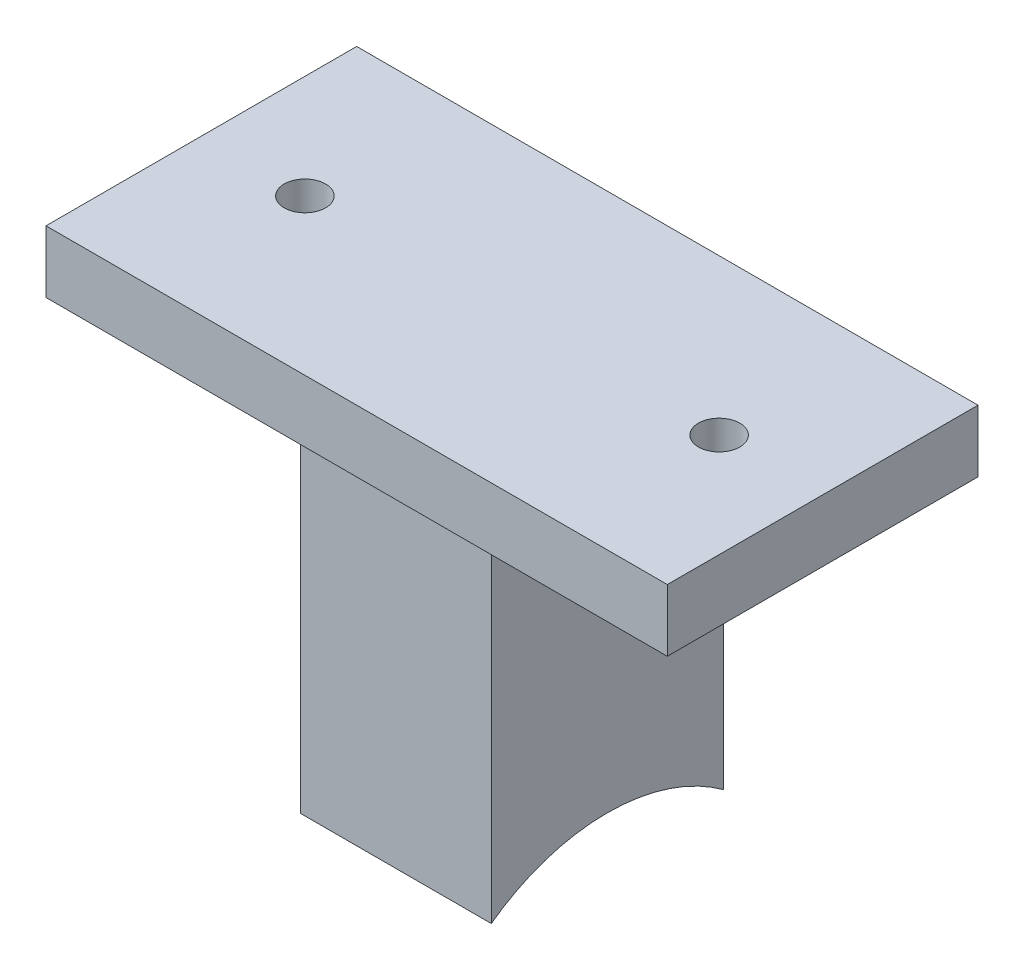
SolidWorks part; units mm, degrees
ref_plane "前视基准面" through (0, 0, 0) normal (0, 0, 1) x (1, 0, 0)
ref_plane "上视基准面" through (0, 0, 0) normal (0, 1, 0) x (1, 0, 0)
ref_plane "右视基准面" through (0, 0, 0) normal (1, 0, 0) x (0, 0, -1)
other "Configuration Table"
sketch "草图1" plane through (0, 0, 0) normal (0, 1, 0) x (1, 0, 0)
  line L1 (-15, -7.5) -> (15, -7.5)
  line L2 (-15, -7.5) -> (-15, 7.5)
  line L3 (-15, 7.5) -> (15, 7.5)
  line L4 (15, -7.5) -> (15, 7.5)
  line L5 (-15, -7.5) -> (15, 7.5) construction
  line L6 (-15, 7.5) -> (15, -7.5) construction
  point P0 (0, 0)
  point P5 (0, 0)
  point P6 (0, 0)
  dimension "D1" = 15
  dimension "D2" = 30
extrude "凸台-拉伸1" add sketch "草图1" along normal blind 3 contours L3 L4 L1 L2
sketch "草图2" plane through (0, 0, 0) normal (0, -1, 0) x (1, 0, 0)
  line L0 (-10, 0) -> (10, 0) construction
  circle A0 centre (-10, 0) radius 1
  circle A1 centre (10, 0) radius 1
  circle A2 centre (-10, 0) radius 1.5
  circle A3 centre (10, 0) radius 1.5
  dimension "D1" = 2
  dimension "D2" = 3
  dimension "D3" = 20
extrude "切除-拉伸1" cut sketch "草图2" against normal through all contours A0 | A1
extrude "切除-拉伸2" cut sketch "草图2<4>" against normal blind 1
sketch "草图2<4>" plane through (0, 0, 0) normal (0, -1, 0) x (1, 0, 0) same geometry as "草图2"
sketch "草图3" plane through (0, 0, 0) normal (0, -1, 0) x (1, 0, 0)
  line L0 (0, 5.6) -> (0, -5.6) construction
  line L1 (-2.7, -2.6) -> (2.7, -2.6)
  line L2 (-2.7, -2.6) -> (-2.7, 2.6)
  line L3 (-2.7, 2.6) -> (2.7, 2.6)
  line L4 (2.7, -2.6) -> (2.7, 2.6)
  line L5 (-2.7, -2.6) -> (2.7, 2.6) construction
  line L6 (-2.7, 2.6) -> (2.7, -2.6) construction
  line L7 (-4.6, 5.6) -> (4.6, 5.6)
  line L8 (-4.6, 5.6) -> (-4.6, -5.6)
  line L9 (-4.6, -5.6) -> (4.6, -5.6)
  line L10 (4.6, 5.6) -> (4.6, -5.6)
  dimension "D1" = 5.4
  dimension "D2" = 5.2
  dimension "D3" = 3
  dimension "D4" = 3
  dimension "D5" = 9.2
extrude "凸台-拉伸2" add sketch "草图3" along normal blind 20
sketch "草图4" plane through (-4.6, 0, 0) normal (-1, 0, 0) x (0, 0, 1)
  circle A0 centre (0, -25) radius 9.5
  point P2 (0, 0)
  dimension "D1" = 19
  dimension "D2" = 25
extrude "切除-拉伸3" cut sketch "草图4" against normal through all
fillet "圆角1" radius 2 2 edges at (0, -15.8627, 2.6) (0, -15.8627, -2.6)
fillet "圆角2" radius 2 2 edges at (2.7, -15.5, 0) (-2.7, -15.5, 0)
